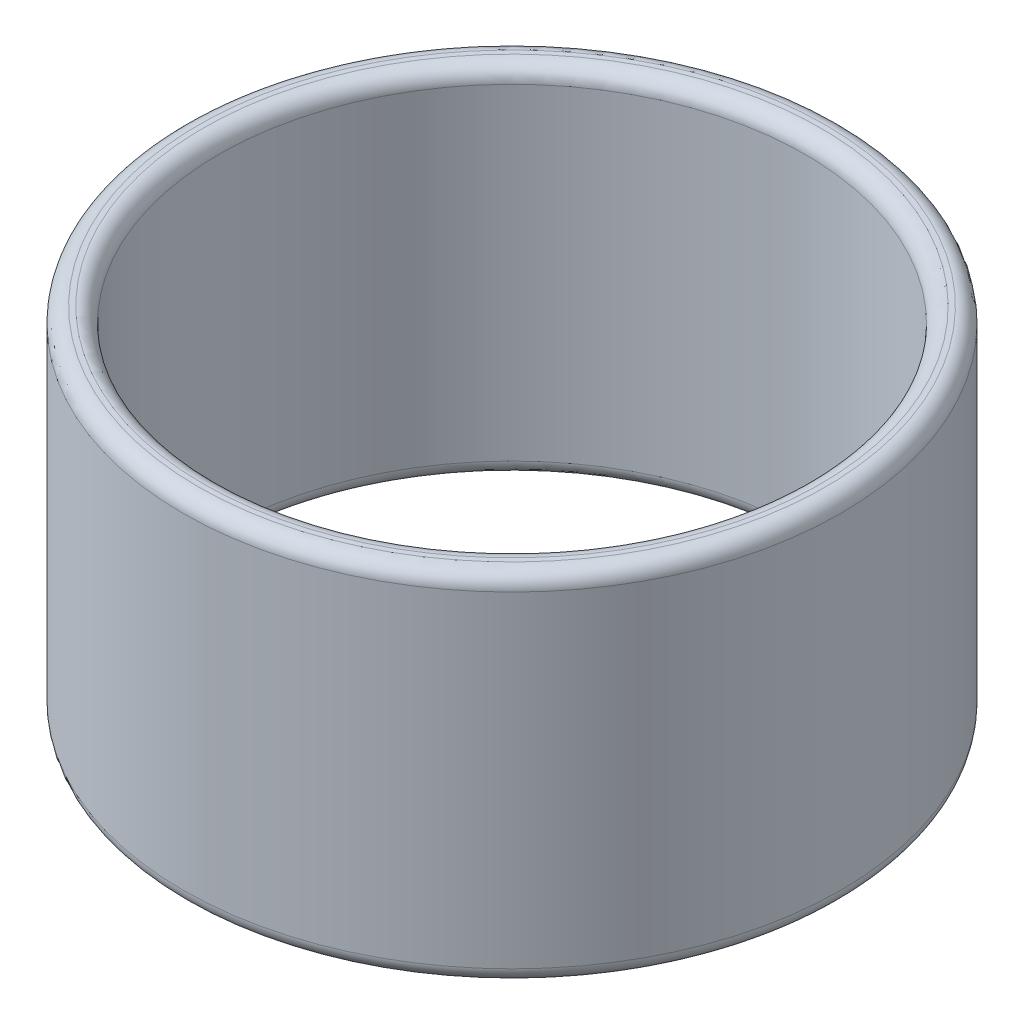
SolidWorks part; units mm, degrees
ref_plane "Front Plane" through (0, 0, 0) normal (0, 0, 1) x (1, 0, 0)
ref_plane "Top Plane" through (0, 0, 0) normal (0, 1, 0) x (1, 0, 0)
ref_plane "Right Plane" through (0, 0, 0) normal (1, 0, 0) x (0, 0, -1)
sketch "Sketch1" plane through (0, 0, 0) normal (0, 1, 0) x (1, 0, 0)
  circle A0 centre (0, 0) radius 12.9
  circle A1 centre (0, 0) radius 11.5
  dimension "D1" = 1.4
  dimension "D2" = 23
extrude "Boss-Extrude1" add sketch "Sketch1" along normal blind 14
fillet "Fillet2" radius 0.6 4 edges at (0, 14, 12.9) (0, 0, 11.5) (0, 14, 11.5) (0, 0, 12.9)
